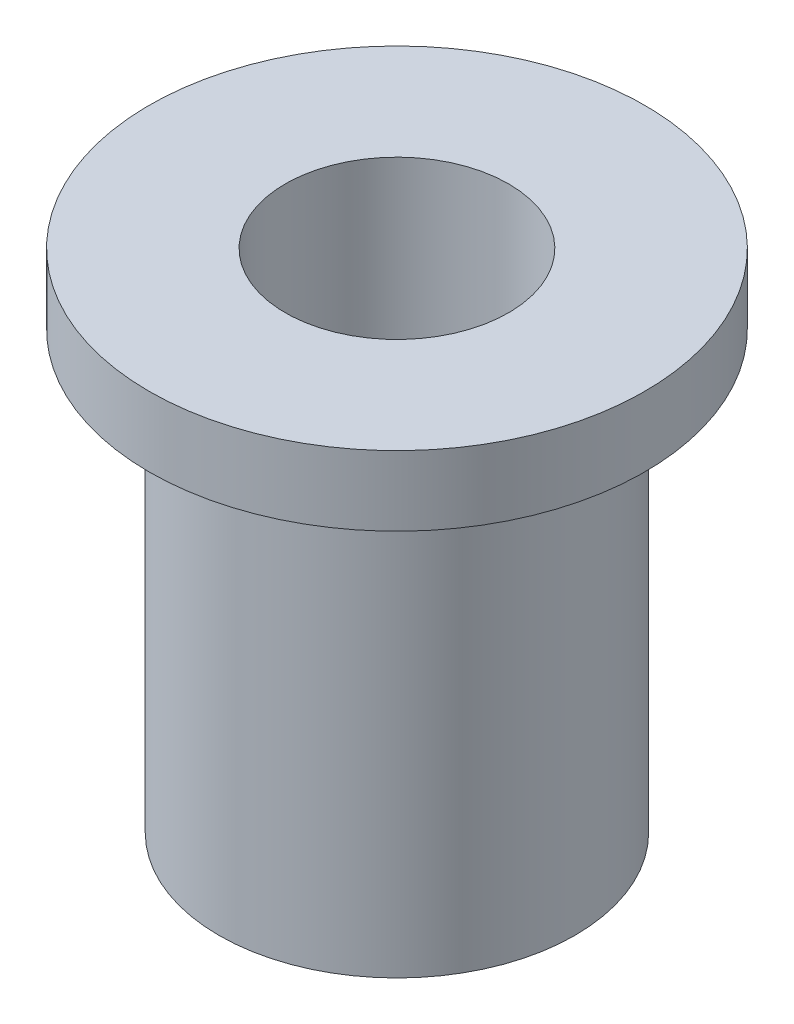
SolidWorks part; units mm, degrees
ref_plane "Front Plane" through (0, 0, 0) normal (0, 0, 1) x (1, 0, 0)
ref_plane "Top Plane" through (0, 0, 0) normal (0, 1, 0) x (1, 0, 0)
ref_plane "Right Plane" through (0, 0, 0) normal (1, 0, 0) x (0, 0, -1)
sketch "Sketch1" plane through (0, 0, 0) normal (0, 1, 0) x (1, 0, 0)
  circle A0 centre (0, 0) radius 2.55
  circle A1 centre (0, 0) radius 1.6
  dimension "D1" = 5.1
  dimension "D2" = 3.2
extrude "Boss-Extrude1" add sketch "Sketch1" along normal blind 7.25
sketch "Sketch2" plane through (0, 7.25, 0) normal (0, 1, 0) x (1, 0, 0)
  circle A0 centre (0, 0) radius 1.6
  circle A1 centre (0, 0) radius 3.55
  circle A2 centre (0, 0) radius 2.55 construction
  dimension "D1" = 1
extrude "Boss-Extrude2" add sketch "Sketch2" against normal blind 1
